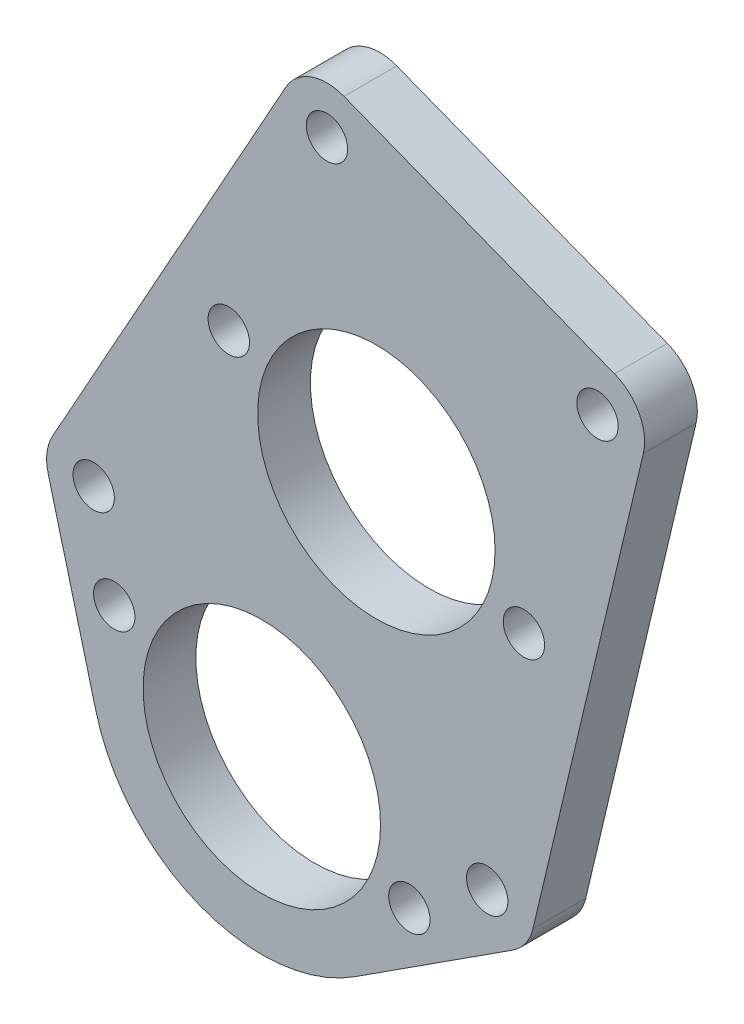
SolidWorks part; units mm, degrees
material "6061-T6 (SS)"
ref_plane "Front Plane" through (0, 0, 0) normal (0, 0, 1) x (1, 0, 0)
ref_plane "Top Plane" through (0, 0, 0) normal (0, 1, 0) x (1, 0, 0)
ref_plane "Right Plane" through (0, 0, 0) normal (1, 0, 0) x (0, 0, -1)
sketch "Sketch1" plane through (0, 0, 0) normal (0, 0, 1) x (1, 0, 0)
  line L0 (13.7841, 35.5191) -> (0, 0) construction
  line L1 (-20.2334, 18.0692) -> (27.1254, -0.3096) construction
  line L2 (13.7841, 35.5191) -> (24.1222, 62.1585) construction
  line L3 (0, 0) -> (23.1556, 0) construction
  line L4 (-25.7114, 16.6288) -> (-19.9591, -5.2481)
  line L5 (11.194, -17.3378) -> (30.1978, -5.0682)
  line L8 (7.8426, 68.4762) -> (40.4018, 55.8408) construction
  line L9 (-25.1818, 20.8254) -> (2.8942, 71.2324)
  line L10 (32.6377, -1.6129) -> (45.914, 54.5374)
  line L11 (9.8918, 73.7567) -> (42.451, 61.1213)
  line L12 (-3.9755, 42.4112) -> (31.5437, 28.6271) construction
  line L13 (-17.7596, 6.892) -> (17.7596, -6.892) construction
  circle A0 centre (0, 0) radius 14.2875
  circle A1 centre (13.7841, 35.5191) radius 14.2875
  circle A2 centre (-20.2334, 18.0692) radius 2.4892
  circle A3 centre (27.1254, -0.3096) radius 2.4892
  arc A5 (-19.9591, -5.2481) -> (11.194, -17.3378) centre (0, 0) ccw
  circle A9 centre (0, 0) radius 20.6375 construction
  circle A10 centre (40.4018, 55.8408) radius 2.4892
  circle A11 centre (7.8426, 68.4762) radius 2.4892
  arc A12 (-25.1818, 20.8254) -> (-25.7114, 16.6288) centre (-20.2334, 18.0692) ccw
  arc A13 (30.1978, -5.0682) -> (32.6377, -1.6129) centre (27.1254, -0.3096) ccw
  arc A14 (45.914, 54.5374) -> (42.451, 61.1213) centre (40.4018, 55.8408) ccw
  arc A15 (9.8918, 73.7567) -> (2.8942, 71.2324) centre (7.8426, 68.4762) ccw
  circle A16 centre (-20.2334, 18.0692) radius 5.6642 construction
  circle A17 centre (27.1254, -0.3096) radius 5.6642 construction
  circle A18 centre (40.4018, 55.8408) radius 5.6642 construction
  circle A19 centre (7.8426, 68.4762) radius 5.6642 construction
  circle A20 centre (-17.7596, 6.892) radius 2.4892
  circle A21 centre (17.7596, -6.892) radius 2.4892
  circle A22 centre (-3.9755, 42.4112) radius 2.4892
  circle A23 centre (31.5437, 28.6271) radius 2.4892
  point P17 (24.1222, 62.1585)
  point P32 (3.446, 8.8798)
  point P47 (0, 0)
  point P48 (13.7841, 35.5191)
  dimension "D1" = 28.575
  dimension "D3" = 4.9784
  dimension "D12" = 4.9784
  dimension "D2" = 38.1
  dimension "D4" = 28.575
  dimension "D5" = 50.8
  dimension "D6" = 68.79
  dimension "D8" = 34.925
  dimension "D10" = 9.525
  dimension "D11" = 38.1
  dimension "D7" = 6.35
  dimension "D9" = 3.175
extrude "Boss-Extrude1" add sketch "Sketch1" along normal mid plane 6.35
equation "\"D2@Sketch1\"=60/40"
